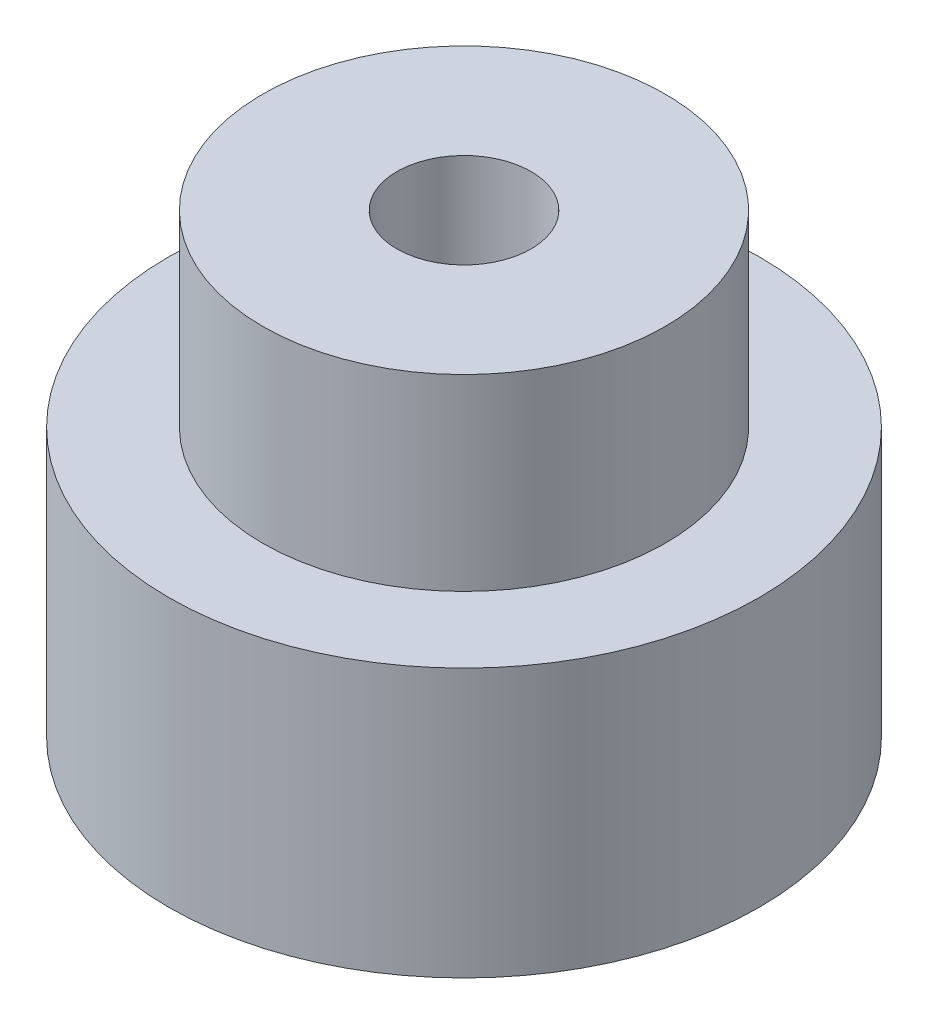
SolidWorks part; units mm, degrees
ref_plane "Front Plane" through (0, 0, 0) normal (0, 0, 1) x (1, 0, 0)
ref_plane "Top Plane" through (0, 0, 0) normal (0, 1, 0) x (1, 0, 0)
ref_plane "Right Plane" through (0, 0, 0) normal (1, 0, 0) x (0, 0, -1)
sketch "Sketch1" plane through (0, 0, 0) normal (0, 1, 0) x (1, 0, 0)
  circle A0 centre (0, 0) radius 11
  circle A1 centre (0, 0) radius 7.5
  circle A2 centre (0, 0) radius 2.5
  dimension "D1" = 22
  dimension "D2" = 15
  dimension "D3" = 5
extrude "Boss-Extrude1" add sketch "Sketch1" against normal blind 10 contours A0
extrude "Boss-Extrude2" add sketch "Sketch1<3>" along normal blind 7 contours A1
sketch "Sketch1<3>" plane through (0, 0, 0) normal (0, 1, 0) x (1, 0, 0) same geometry as "Sketch1"
extrude "Cut-Extrude1" cut sketch "Sketch1<4>" against normal blind 11 and the other way blind 10 contours A2
sketch "Sketch1<4>" plane through (0, 0, 0) normal (0, 1, 0) x (1, 0, 0) same geometry as "Sketch1"
